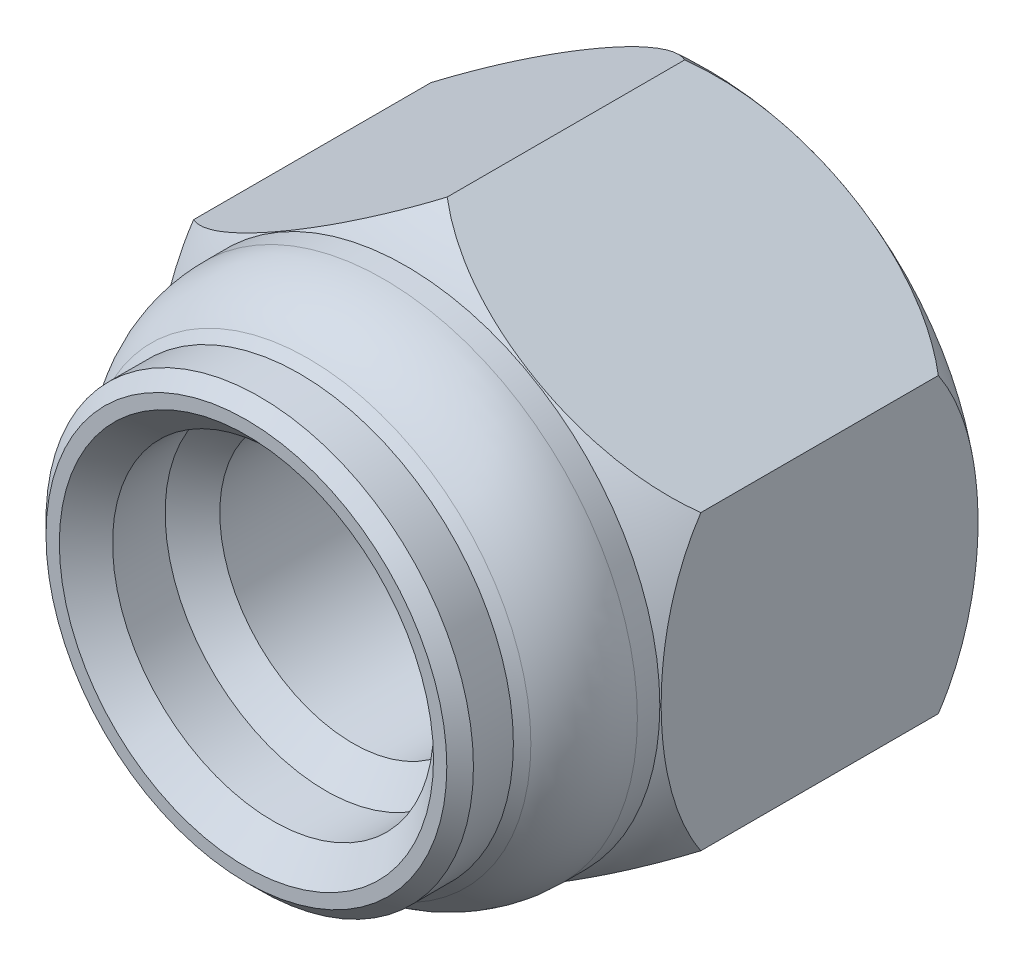
SolidWorks part; units mm, degrees
ref_plane "Front Plane" through (0, 0, 0) normal (0, 0, 1) x (1, 0, 0)
ref_plane "Top Plane" through (0, 0, 0) normal (0, 1, 0) x (1, 0, 0)
ref_plane "Right Plane" through (0, 0, 0) normal (1, 0, 0) x (0, 0, -1)
sketch "Sketch1" plane through (0, 0, 0) normal (0, 0, 1) x (1, 0, 0)
  line L1 (4.7631, -2.75) -> (4.7631, 2.75)
  line L2 (4.7631, 2.75) -> (0, 5.5)
  line L3 (0, 5.5) -> (-4.7631, 2.75)
  line L4 (-4.7631, 2.75) -> (-4.7631, -2.75)
  line L5 (-4.7631, -2.75) -> (0, -5.5)
  line L6 (0, -5.5) -> (4.7631, -2.75)
  circle A0 centre (0, 0) radius 4.7631 construction
  circle A1 centre (0, 0) radius 2
  dimension "D2" = 4
  dimension "D1" = 5.5
extrude "Boss-Extrude1" add sketch "Sketch1" along normal blind 6
sketch "Sketch3" plane through (0, 0, 0) normal (1, 0, 0) x (0, 0, -1)
  line L0 (-6.75, 2.25) -> (-6.75, 6.25)
  line L1 (-6.75, 6.25) -> (-2.75, 6.25)
  line L4 (-6, 5.5) -> (0, 5.5) construction
  line L5 (-6, 2.75) -> (-6, 5.5) construction
  line L6 (-3, -5.5) -> (-3, 5.5) construction
  line L7 (-6, -5.5) -> (0, -5.5) construction
  line L8 (0, 0) -> (-6, 0) construction
  line L9 (-6, -2.75) -> (-6, 2.75) construction
  line L10 (0.75, 2.25) -> (0.75, 6.25)
  line L11 (0.75, 6.25) -> (-3.25, 6.25)
  arc A0 (-6.75, 2.25) -> (-2.75, 6.25) centre (-2.9556, 2.4556) cw
  arc A1 (0.75, 2.25) -> (-3.25, 6.25) centre (-3.0444, 2.4556) ccw
  dimension "D2" = 3.8
  dimension "D3" = 0.75
  dimension "D1" = 4
  dimension "D4" = 0.75
revolve "Cut-Revolve1" cut sketch "Sketch3" angle 360 about L8 region at (0, 5.4077, 5.9077) region at (0, 5.4077, 0.0923)
sketch "Sketch4" plane through (0, 0, 6) normal (0, 0, 1) x (1, 0, 0)
  line L1 (-4.7631, 2.75) -> (-4.7631, -2.75) construction
  circle A0 centre (0, 0) radius 4.7631
extrude "Boss-Extrude2" add sketch "Sketch4" along normal blind 2
chamfer "Chamfer1" distance 0.75 angle 45 1 edges at (4.7631, 0, 8)
sketch "Sketch6" plane through (0, 0, 8) normal (0, 0, 1) x (1, 0, 0)
  circle A1 centre (0, 0) radius 4.0131
  circle A2 centre (0, 0) radius 4.0131 construction
  circle A3 centre (0, 0) radius 3.0131
  dimension "D1" = 1
extrude "Boss-Extrude3" add sketch "Sketch6" along normal blind 1
chamfer "Chamfer2" distance 0.5 angle 45 1 edges at (3.0131, 0, 9)
chamfer "Chamfer3" distance 0.25 angle 45 1 edges at (4.0131, 0, 9)
fillet "Fillet1" radius 2 1 edges at (4.7631, 0, 7.25)
sketch "Sketch7" plane through (0, 0, 8) normal (0, 0, 1) x (1, 0, 0)
  circle A1 centre (0, 0) radius 3.0131 construction
  circle A2 centre (0, 0) radius 2.5
  dimension "D1" = 5
extrude "Cut-Extrude2" cut sketch "Sketch7" against normal up to surface (8 mm away) and the other way through all up to face at (2, 0, 0)
chamfer "Chamfer4" distance 1 angle 45 1 edges at (2.5, 0, 8)
